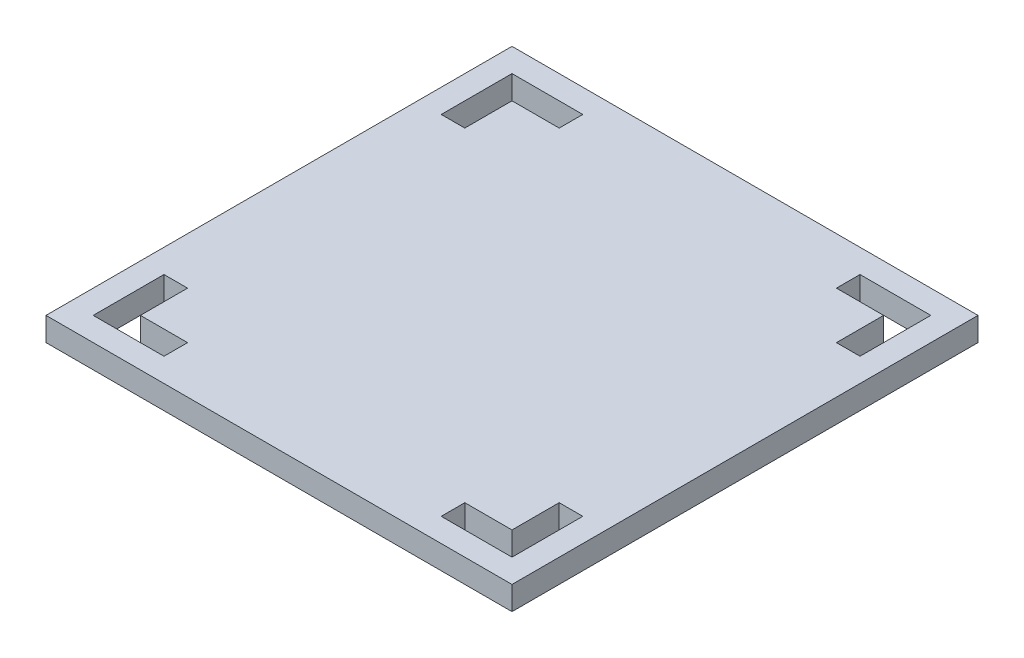
SolidWorks part; units mm, degrees
material "Acrylic (Medium-high impact)"
ref_plane "Front Plane" through (0, 0, 0) normal (0, 0, 1) x (1, 0, 0)
ref_plane "Top Plane" through (0, 0, 0) normal (0, 1, 0) x (1, 0, 0)
ref_plane "Right Plane" through (0, 0, 0) normal (1, 0, 0) x (0, 0, -1)
sketch "Sketch1" plane through (0, 0, 0) normal (0, 1, 0) x (1, 0, 0)
  line L1 (-62.7, -62.7) -> (62.7, -62.7)
  line L2 (-62.7, -62.7) -> (-62.7, 62.7)
  line L3 (-62.7, 62.7) -> (62.7, 62.7)
  line L4 (62.7, -62.7) -> (62.7, 62.7)
  line L5 (-62.7, -62.7) -> (62.7, 62.7) construction
  line L6 (-62.7, 62.7) -> (62.7, -62.7) construction
  point P0 (0, 0)
  dimension "D1" = 125.4
  dimension "D2" = 125.4
extrude "Boss-Extrude1" add sketch "Sketch1" along normal blind 6.35
sketch "Sketch2" plane through (0, 6.35, 0) normal (0, 1, 0) x (1, 0, 0)
  line L1 (-50, -50) -> (50, -50)
  line L2 (-50, -50) -> (-50, 50)
  line L3 (-50, 50) -> (50, 50)
  line L4 (50, -50) -> (50, 50)
  line L5 (-50, -50) -> (50, 50) construction
  line L6 (-50, 50) -> (50, -50) construction
  point P0 (0, 0)
  dimension "D1" = 100
  dimension "D2" = 100
sketch "Sketch4" plane through (0, 6.35, 0) normal (0, 1, 0) x (1, 0, 0)
  line L1 (-50, 50) -> (-56.35, 50)
  line L2 (-50, 50) -> (-50, 37.3)
  line L3 (-50, 37.3) -> (-56.35, 37.3)
  line L4 (-56.35, 50) -> (-56.35, 37.3)
  dimension "D1" = 6.35
  dimension "D2" = 12.7
extrude "Cut-Extrude1" cut sketch "Sketch4" against normal through all
sketch "Sketch5" plane through (0, 6.35, 0) normal (0, 1, 0) x (1, 0, 0)
  line L1 (-56.35, 50) -> (-37.3, 50)
  line L2 (-56.35, 50) -> (-56.35, 56.35)
  line L3 (-56.35, 56.35) -> (-37.3, 56.35)
  line L4 (-37.3, 50) -> (-37.3, 56.35)
  dimension "D1" = 19.05
  dimension "D2" = 6.35
extrude "Cut-Extrude2" cut sketch "Sketch5" against normal through all
ref_axis "Axis1" through (0, 6.35, 0) along (0, 1, 0)
pattern_circular "CirPattern1" count 4 every 90 about axis through (0, 6.35, 0) along (0, 1, 0) of "Cut-Extrude1"
pattern_circular "CirPattern2" count 4 every 90 about axis through (0, 6.35, 0) along (0, 1, 0) of "Cut-Extrude2"
